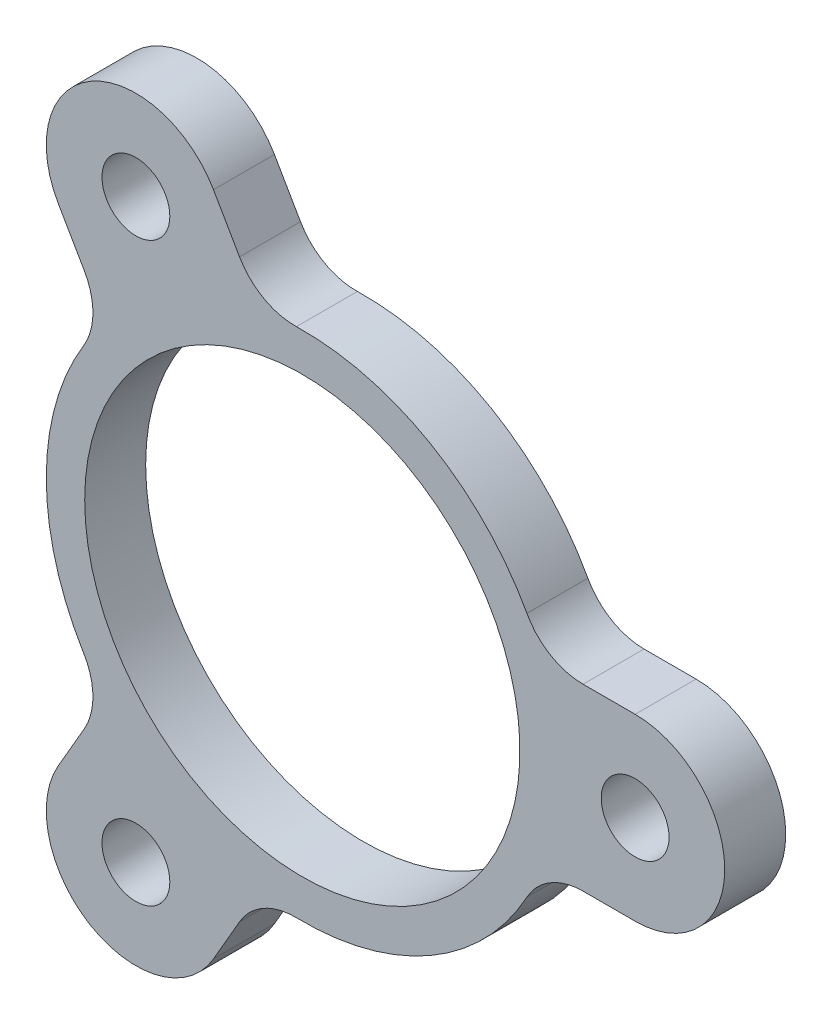
SolidWorks part; units mm, degrees
ref_plane "Front Plane" through (0, 0, 0) normal (0, 0, 1) x (1, 0, 0)
ref_plane "Top Plane" through (0, 0, 0) normal (0, 1, 0) x (1, 0, 0)
ref_plane "Right Plane" through (0, 0, 0) normal (1, 0, 0) x (0, 0, -1)
ref_plane "Plane1" through (0, 0, 94.7) normal (0, 0, 1) x (1, 0, 0)
sketch "Sketch1" plane through (0, 0, 94.7) normal (0, 0, 1) x (1, 0, 0)
  line L0 (0, 0) -> (26, 0) construction
  line L1 (26, 7) -> (18.735, 7)
  line L2 (26, -7) -> (18.735, -7)
  line L3 (-6.9378, -26.0167) -> (-3.3053, -19.725)
  line L4 (-19.0622, -19.0167) -> (-15.4297, -12.725)
  line L5 (-19.0622, 19.0167) -> (-15.4297, 12.725)
  line L6 (-6.9378, 26.0167) -> (-3.3053, 19.725)
  circle A1 centre (26, 0) radius 3 construction
  circle A2 centre (0, 0) radius 17
  arc A4 (26, 7) -> (26, -7) centre (26, 0) cw
  arc A5 (-15.4297, 12.725) -> (-15.4297, -12.725) centre (0, 0) ccw
  arc A6 (-6.9378, -26.0167) -> (-19.0622, -19.0167) centre (-13, -22.5167) cw
  arc A7 (-19.0622, 19.0167) -> (-6.9378, 26.0167) centre (-13, 22.5167) cw
  arc A8 (18.735, 7) -> (-3.3053, 19.725) centre (0, 0) ccw
  arc A9 (-3.3053, -19.725) -> (18.735, -7) centre (0, 0) ccw
  point P0 (26, 0)
  point P4 (-13, -22.5167)
  point P5 (-13, 22.5167)
  point P6 (0, 0)
  point P11 (33, 0)
  dimension "D3" = 6
  dimension "D4" = 34
  dimension "D5" = 40
  dimension "D6" = 7
  dimension "D7" = 7
  dimension "D2" = 26
  dimension "D1" = 3
  dimension "D8" = 3
extrude "Boss-Extrude1" add sketch "Sketch1" along normal blind 4.7625 contours A4 A2 region at (32.2067, 0, 94.7)
hole_wizard "M5 Clearance Hole1" positions "Sketch2" profile "Sketch4" hole size "M5" standard "ANSI Metric" end condition through all
sketch "Sketch2" plane through (0, 0, 99.4625) normal (0, 0, 1) x (1, 0, 0)
  point P0 (-13, 22.5167)
  point P3 (26, 0)
  point P6 (-13, -22.5167)
sketch "Sketch4" plane through (-13, 22.5167, 99.4625) normal (1, 0, 0) x (0, -1, 0)
  line L0 (0, 0) -> (0, 4.7625)
  line L1 (0, 4.7625) -> (2.65, 4.7625)
  line L2 (2.65, 4.7625) -> (2.65, 0)
  line L5 (2.65, 0) -> (0, 0)
  line L11 (0, -6.35) -> (0, 107.95) construction
  dimension "Thru Hole Dia." = 5.3
  dimension "Thru Hole Depth" = 4.7625
fillet "Fillet1" radius 5 6 edges at (-3.3053, -19.725, 97.0813) (18.735, -7, 97.0813) (18.735, 7, 97.0813) (-3.3053, 19.725, 97.0813) (-15.4297, 12.725, 97.0813) (-15.4297, -12.725, 97.0813)
